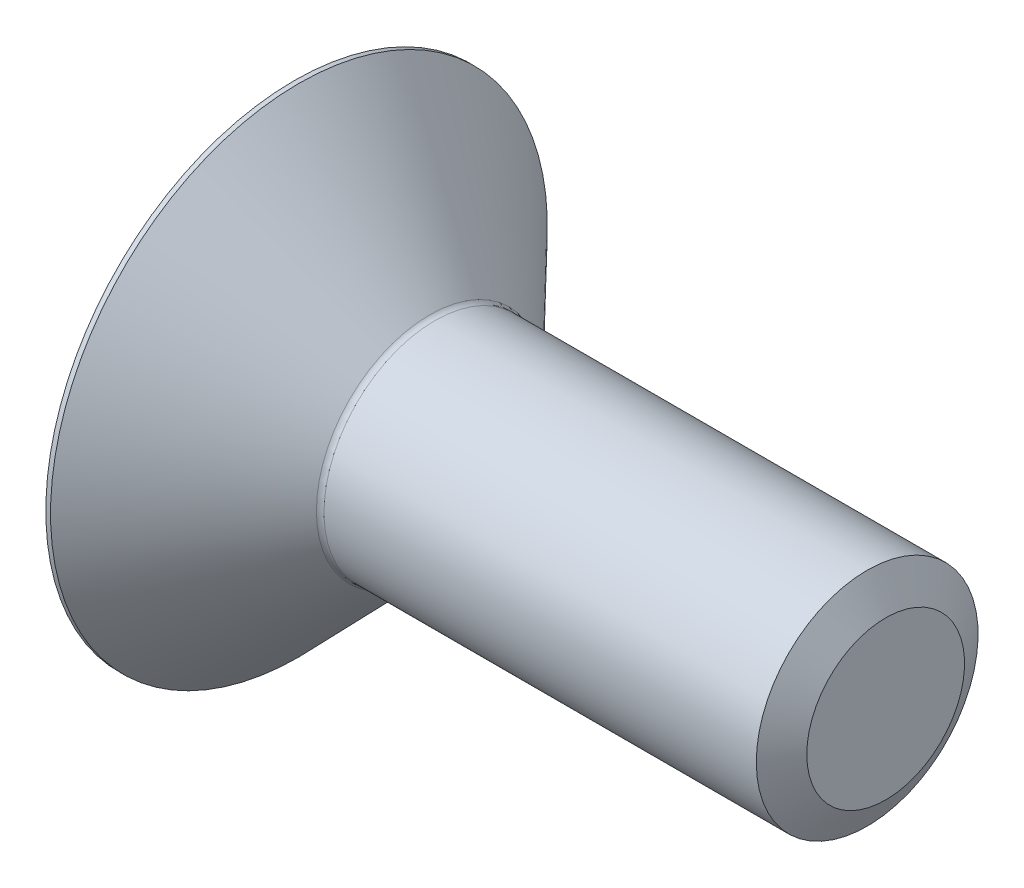
SolidWorks part; units mm, degrees
ref_plane "前视基准面" through (0, 0, 0) normal (0, 0, 1) x (1, 0, 0)
ref_plane "上视基准面" through (0, 0, 0) normal (0, 1, 0) x (1, 0, 0)
ref_plane "右视基准面" through (0, 0, 0) normal (1, 0, 0) x (0, 0, -1)
sketch "尺寸草图" plane through (0, 0, 0) normal (0, 0, 1) x (1, 0, 0)
  line L0 (0, 0) -> (8, 0) construction
  line L1 (8, 0) -> (8, 1.5) construction
  line L2 (8, 1.5) -> (7.5, 1.5) construction
  line L3 (7.5, 1.5) -> (2, 1.5) construction
  line L4 (0, 3.36) -> (1.86, 3.36) construction
  line L5 (1.86, 3.36) -> (1.96, 3.36) construction
  point P3 (8, 1.65)
  point P7 (0, 3.36)
  point P8 (0, 1.5)
  point P9 (0, 2.3)
  point P13 (0, 1)
  point P15 (1.1, 3.36)
  point P16 (1.71, 3.36)
  dimension "l" = 8
  dimension "d" = 3
  dimension "P" = 0.5
  dimension "b" = 6
  dimension "da" = 3.3
  dimension "dk" = 6.72
  dimension "ds" = 3
  dimension "e" = 2.3
  dimension "k" = 1.86
  dimension "r" = 0.1
  dimension "s" = 2
  dimension "t" = 1.1
  dimension "w" = 0.25
sketch "草图1" plane through (0, 0, 0) normal (0, 0, 1) x (1, 0, 0)
  line L0 (0, 1.5) -> (-6.0976, 1.5)
  line L1 (-6.1695, 1.5305) -> (-7.9362, 3.36)
  line L2 (-7.9362, 3.36) -> (-8, 3.36)
  line L3 (-8, 3.36) -> (-8, 0)
  line L4 (-8, 0) -> (0, 0)
  line L5 (0, 0) -> (0, 1.5)
  line L6 (0, 0) -> (-8, 0) construction
  arc A0 (-6.0976, 1.5) -> (-6.1695, 1.5305) centre (-6.0976, 1.6) cw
  point P9 (-6.14, 1.5)
  dimension "r" = 0.1
  dimension "k" = 1.86
  dimension "dk" = 6.72
  dimension "l" = 8
  dimension "D5" = 46
  dimension "d" = 3
revolve "旋转1" add sketch "草图1" angle 360 about L6
cosmetic thread "装饰螺纹线1" parameters "b"=6, "D2"=2.4
sketch "草图2" plane through (-8, 0, 0) normal (-1, 0, 0) x (0, 0, 1)
  line L0 (0, 0) -> (0, 1.5) construction
  line L1 (0, 1.1547) -> (-1, 0.5774)
  line L2 (-1, 0.5774) -> (-1, -0.5774)
  line L3 (-1, -0.5774) -> (0, -1.1547)
  line L4 (0, -1.1547) -> (1, -0.5774)
  line L5 (1, -0.5774) -> (1, 0.5774)
  line L6 (1, 0.5774) -> (0, 1.1547)
  circle A0 centre (0, 0) radius 1 construction
  point P1 (0, 1.1453)
  dimension "s" = 2
  dimension "e" = 2.3
extrude "切除-拉伸1" cut sketch "草图2" against normal blind 1.86
sketch "草图6" plane through (0, 0, 0) normal (0, 0, 1) x (1, 0, 0)
  line L0 (-6.9, 1.1547) -> (-6.2333, 0)
  line L1 (-6.2333, 0) -> (-5.84, 0)
  line L2 (-5.84, 0) -> (-5.84, 1.1547)
  line L3 (-5.84, 1.1547) -> (-6.9, 1.1547)
  line L4 (-8, 0) -> (-6.14, 0) construction
  line L5 (-8, 0) -> (-10.3, 0) construction
  dimension "D1" = 60
  dimension "t" = 1.1
  dimension "t1" = 1.86
  dimension "e-s" = 0.3
  dimension "e" = 2.3
revolve "旋转2" add sketch "草图6" angle 360 about L4
sketch "草图7" plane through (0, 0, 0) normal (0, 0, 1) x (1, 0, 0)
  line L0 (-8, 1.1547) -> (-8, 0)
  line L1 (-8, 0) -> (-7.7, 0)
  line L2 (-7.7, 0) -> (-8, 1.1547)
  line L3 (-8, 0) -> (-7.7, 0) construction
  dimension "e-s*1.1" = 0.3
revolve "切除-旋转2" cut sketch "草图7" angle 360 about L3
sketch "草图4" plane through (0, 0, 0) normal (0, 0, 1) x (1, 0, 0)
  line L0 (-0.25, 1.5) -> (0, 1.067)
  line L1 (0, -1.5) -> (0, 1.5) construction
  line L2 (0, 1.067) -> (0.25, 1.5)
  line L3 (0.25, 1.5) -> (-0.25, 1.5)
  line L4 (-0.25, 0) -> (0.25, 0) construction
  dimension "d" = 3
  dimension "p" = 0.5
revolve "切除-旋转1" cut sketch "草图4" angle 360 about L4
ref_axis "基准轴1" through (-21.1715, 0, 0) along (1, 0, 0)
pattern_linear "阵列(线性)2" [suppressed] count 12 spacing 0.5 along (-1, 0, 0) of bodies 104
